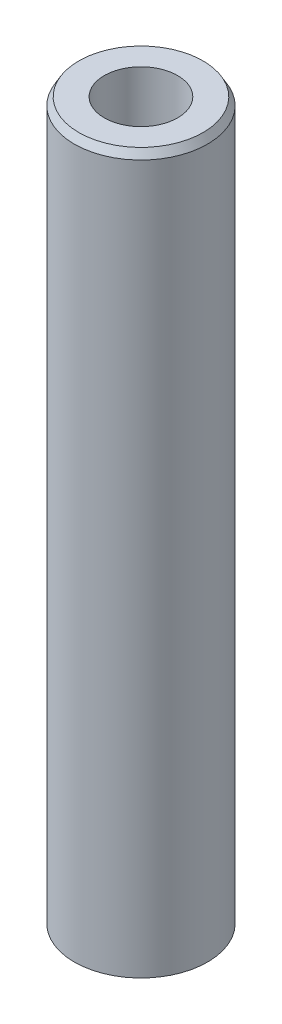
SolidWorks part; units mm, degrees
ref_plane "Front Plane" through (0, 0, 0) normal (0, 0, 1) x (1, 0, 0)
ref_plane "Top Plane" through (0, 0, 0) normal (0, 1, 0) x (1, 0, 0)
ref_plane "Right Plane" through (0, 0, 0) normal (1, 0, 0) x (0, 0, -1)
sketch "Sketch1" plane through (0, 0, 0) normal (0, 1, 0) x (1, 0, 0)
  circle A0 centre (0, 0) radius 22.5
  dimension "SHAFT_OD" = 45
extrude "Boss-Extrude1" add sketch "Sketch1" along normal blind 243.4463
sketch "Sketch2" plane through (0, 0, 0) normal (0, 1, 0) x (1, 0, 0)
  circle A0 centre (0, 0) radius 12.3913
  dimension "BORE_D" = 24.7826
extrude "Cut-Extrude1" cut sketch "Sketch2" along normal through all
chamfer "Chamfer1" distance 2.6288 angle 30 2 edges at (0, 243.4463, 22.5) (0, 0, 22.5) first distance on face at (0, 243.4463, 22.5) first distance on face at (0, 0, 12.3913)
